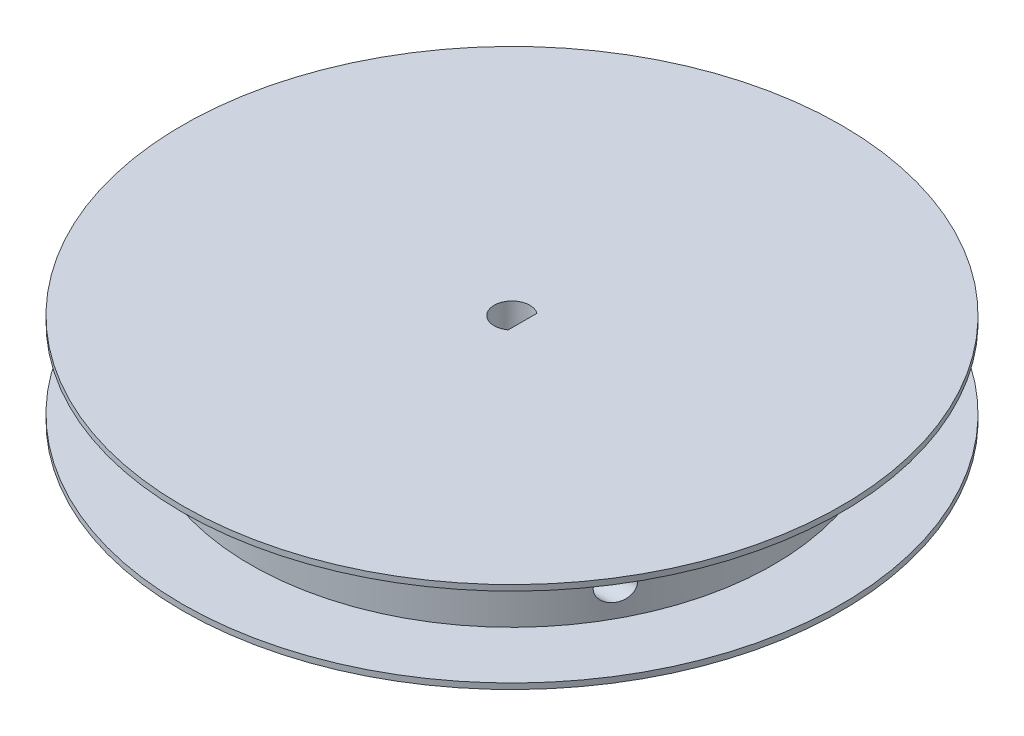
SolidWorks part; units mm, degrees
ref_plane "前基準面" through (0, 0, 0) normal (0, 0, 1) x (1, 0, 0)
ref_plane "上基準面" through (0, 0, 0) normal (0, 1, 0) x (1, 0, 0)
ref_plane "右基準面" through (0, 0, 0) normal (1, 0, 0) x (0, 0, -1)
sketch "草圖1" plane through (0, 0, 0) normal (0, 1, 0) x (1, 0, 0)
  circle A0 centre (0, 0) radius 9
  dimension "D1" = 18
extrude "填料-伸長1" add sketch "草圖1" against normal blind 8
sketch "草圖2" plane through (0, -8, 0) normal (0, -1, 0) x (-1, 0, 0)
  line L1 (-0.93, -1.2649) -> (-0.93, 1.2649)
  circle A0 centre (0, 0) radius 1.57
extrude "除料-伸長1" cut sketch "草圖2" against normal through all contours L1 A0 region at (-0.2041, -8, 0)
sketch "草圖3" plane through (0, -8, 0) normal (0, -1, 0) x (-1, 0, 0)
  circle A0 centre (0, 0) radius 14
  circle A1 centre (0, 0) radius 9
sketch "草圖5" plane through (0, 0, 0) normal (0, 1, 0) x (-1, 0, 0)
  circle A0 centre (0, 0) radius 14
  circle A1 centre (0, 0) radius 9
  dimension "D1" = 28
sketch "草圖6" plane through (0, 0, 0) normal (1, 0, 0) x (0, 0, -1)
  circle A0 centre (-8.2974, 2.581) radius 0.4984
sketch "草圖7" plane through (0, -8, 0) normal (0, -1, 0) x (-1, 0, 0)
  circle A0 centre (0, 0) radius 9
  circle A1 centre (0, 0) radius 23
extrude "填料-伸長2" add sketch "草圖7" against normal blind 8
sketch "草圖8" plane through (0, 0, 0) normal (0, 1, 0) x (1, 0, 0)
  circle A0 centre (0, 0) radius 29
  circle A1 centre (0, 0) radius 23
extrude "填料-伸長3" add sketch "草圖8" against normal blind 0.5
sketch "草圖9" plane through (0, -8, 0) normal (0, -1, 0) x (1, 0, 0)
  circle A0 centre (0, 0) radius 23
  circle A1 centre (0, 0) radius 29
extrude "填料-伸長4" add sketch "草圖9" against normal blind 0.5
sketch "草圖10" plane through (0, 0, 0) normal (1, 0, 0) x (0, 0, -1)
  circle A0 centre (-11.0333, -4.9876) radius 1.2598
extrude "除料-伸長2" cut sketch "草圖10" against normal mid plane 50
